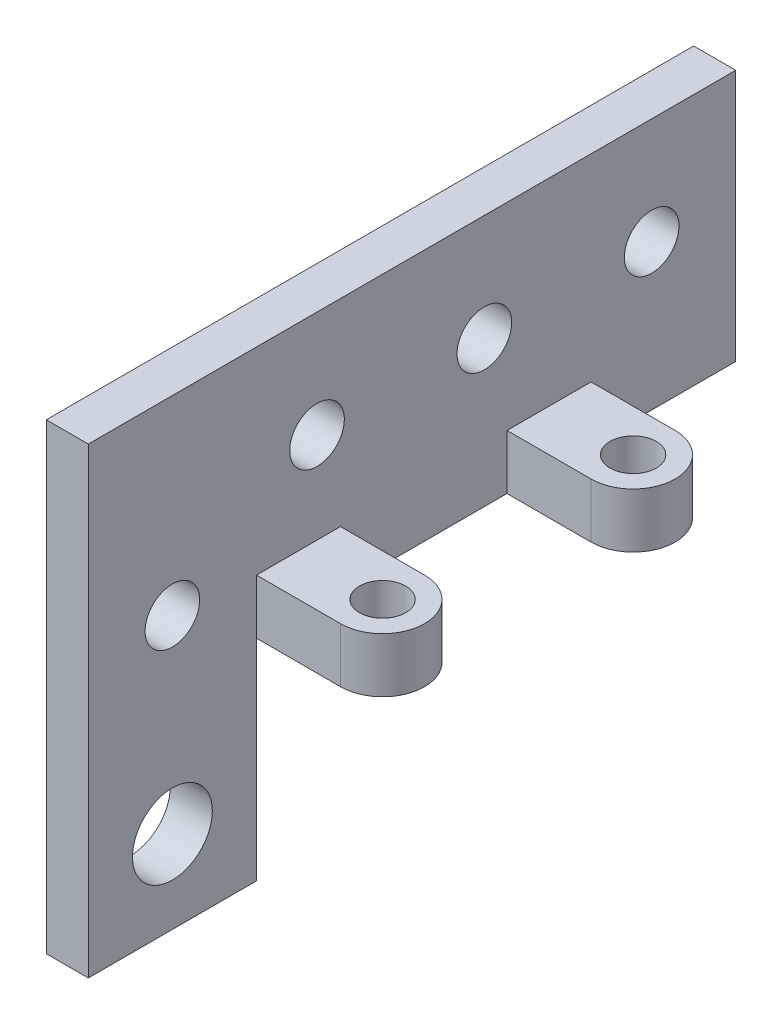
SolidWorks part; units mm, degrees
ref_plane "Front Plane" through (0, 0, 0) normal (0, 0, 1) x (1, 0, 0)
ref_plane "Top Plane" through (0, 0, 0) normal (0, 1, 0) x (1, 0, 0)
ref_plane "Right Plane" through (0, 0, 0) normal (1, 0, 0) x (0, 0, -1)
sketch "Sketch1" plane through (0, 0, 0) normal (1, 0, 0) x (0, 0, -1)
  line L0 (-77.0049, 0) -> (-77.0049, -25)
  line L1 (0, 0) -> (-77.0049, 0)
  line L2 (0, 0) -> (0, 30)
  line L3 (0, 30) -> (-77.0049, 30)
  line L4 (-77.0049, 0) -> (-77.0049, 30)
  line L5 (-77.0049, -25) -> (-67.0049, -25)
  line L6 (-67.0049, -25) -> (-57.0049, -25)
  line L7 (-57.0049, -25) -> (-57.0049, 0)
  circle A2 centre (-67.0049, -15.16) radius 4.75
  circle A5 centre (-29.9, 17.34) radius 3.25
  circle A6 centre (-10, 17.34) radius 3.25
  circle A7 centre (-67.0049, 7.34) radius 3.25
  circle A8 centre (-49.8, 17.34) radius 3.25
  point P11 (0, 0)
  dimension "D3" = 19.9
  dimension "D4" = 10
  dimension "D10" = 9.5
  dimension "D12" = 10
  dimension "D6" = 19.9
  dimension "D7" = 19.9
  dimension "D5" = 22.5
  dimension "D13" = 6.5
  dimension "D2" = 30
  dimension "D8" = 15.16
  dimension "D9" = 10
  dimension "D11" = 25
extrude "Boss-Extrude1" add sketch "Sketch1" along normal blind 5 contours L4 L1 L2 L3 A5 A2 A7 A8 | L6 L7 L1 L0 L5 region at (0, -0.3202, 67.0049) region at (0, 15.0098, 38.4614)
sketch "Sketch2" plane through (5, 0, 0) normal (1, 0, 0) x (0, 0, -1)
  line L0 (0, 0) -> (-38.5025, 0) construction
  line L1 (0, 0) -> (-57.0049, 0) construction
  line L2 (-77.0049, -25) -> (-77.0049, 30) construction
  line L10 (-38.5025, 0) -> (-77.0049, 0) construction
  line L19 (-57.0049, 6.5) -> (-57.0049, 0)
  line L20 (-57.0049, 6.5) -> (-47.0049, 6.5)
  line L21 (-47.0049, 6.5) -> (-47.0049, 0)
  line L22 (-47.0049, 0) -> (-57.0049, 0)
  line L23 (-27.2049, 0) -> (-27.2049, 6.5)
  line L24 (-27.2049, 6.5) -> (-17.2049, 6.5)
  line L25 (-17.2049, 6.5) -> (-17.2049, 0)
  line L26 (-17.2049, 0) -> (-27.2049, 0)
  dimension "D2" = 19.8
  dimension "D1" = 20
  dimension "D3" = 10
  dimension "D4" = 6.5
extrude "Boss-Extrude2" add sketch "Sketch2" along normal blind 10 contours L24 L25 L26 L23 | L22 L19 L20 L21
sketch "Sketch3" plane through (0, 6.5, 0) normal (0, 1, 0) x (1, 0, 0)
  line L0 (15, -47.0049) -> (15, -57.0049)
  line L1 (15, -47.0049) -> (15, -27.2049) construction
  line L2 (11.7918, -37.1049) -> (18.8574, -37.1049) construction
  line L3 (15, -27.2049) -> (15, -17.2049)
  arc A0 (15, -47.0049) -> (15, -57.0049) centre (15, -52.0049) cw
  circle A1 centre (15, -52.0049) radius 2.75
  circle A2 centre (15, -22.2049) radius 2.75
  arc A3 (15, -27.2049) -> (15, -17.2049) centre (15, -22.2049) ccw
  dimension "D1" = 5.5
extrude "Boss-Extrude3" add sketch "Sketch3" against normal up to surface (6.5 mm away) contours A0 L0 | A3 L3 up to face at (7.7273, 0, 32.1677)
extrude "Cut-Extrude1" cut sketch "Sketch3<7>" against normal blind 10 contours L0 A1 | L0 A1 | A2 L3 | A2 L3 region at (16.1671, 6.5, 52.0049) region at (13.8329, 6.5, 52.0049) region at (13.8329, 6.5, 22.2049) region at (16.1671, 6.5, 22.2049)
sketch "Sketch3<7>" plane through (0, 6.5, 0) normal (0, 1, 0) x (1, 0, 0) same geometry as "Sketch3"
